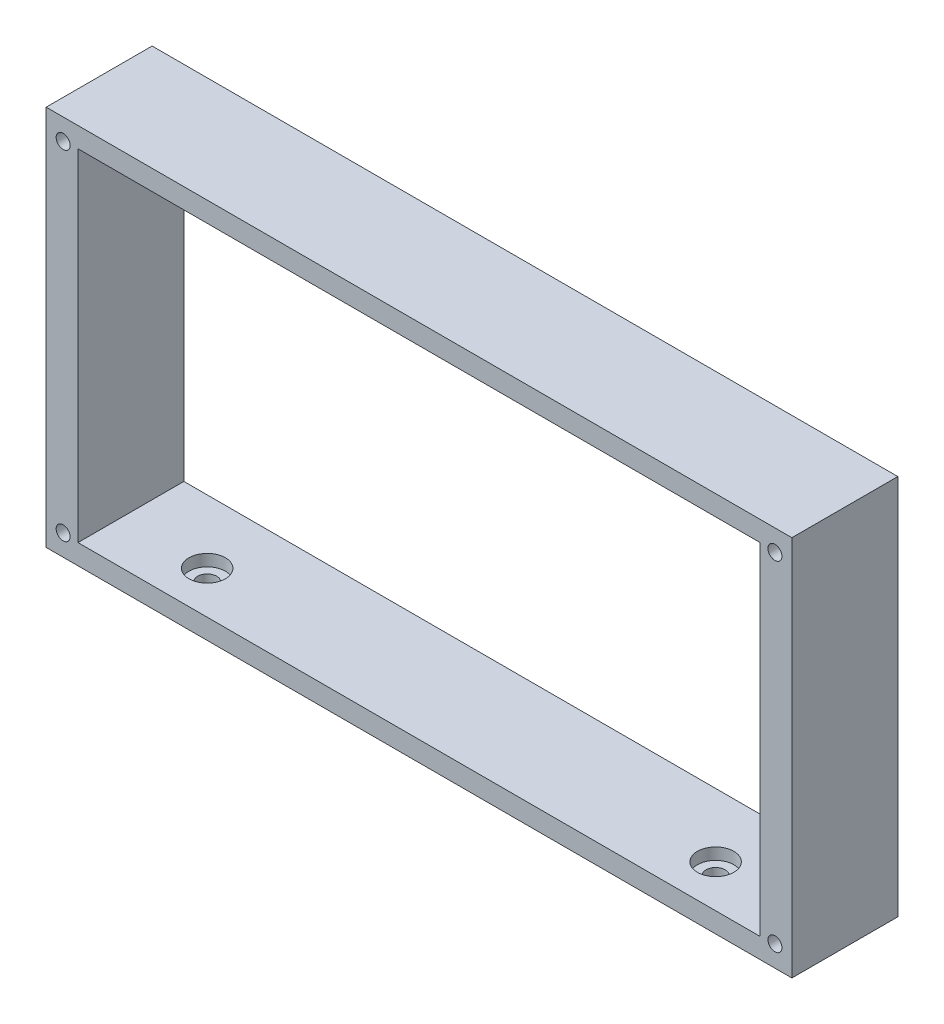
SolidWorks part; units mm, degrees
ref_plane "Front Plane" through (0, 0, 0) normal (0, 0, 1) x (1, 0, 0)
ref_plane "Top Plane" through (0, 0, 0) normal (0, 1, 0) x (1, 0, 0)
ref_plane "Right Plane" through (0, 0, 0) normal (1, 0, 0) x (0, 0, -1)
sketch "Sketch5" plane through (0, 0, 0) normal (0, 0, 1) x (1, 0, 0)
  line L1 (-80.5, -40.25) -> (80.5, -40.25)
  line L2 (-80.5, -40.25) -> (-80.5, 40.25)
  line L3 (-80.5, 40.25) -> (80.5, 40.25)
  line L4 (80.5, -40.25) -> (80.5, 40.25)
  line L5 (-80.5, -40.25) -> (80.5, 40.25) construction
  line L6 (-80.5, 40.25) -> (80.5, -40.25) construction
  line L7 (-88, -45) -> (88, -45)
  line L8 (-88, -45) -> (-88, 45)
  line L9 (-88, 45) -> (88, 45)
  line L10 (88, -45) -> (88, 45)
  line L11 (-88, -45) -> (88, 45) construction
  line L12 (-88, 45) -> (88, -45) construction
  point P0 (0, 0)
  point P6 (0, 0)
  dimension "D1" = 161
  dimension "D2" = 80.5
  dimension "D3" = 176
  dimension "D4" = 90
extrude "Boss-Extrude2" add sketch "Sketch5" along normal blind 25
hole_wizard "M4x0.7 Tapped Hole1" positions "Sketch6" profile "Sketch7" tap size "M4x0.7" standard "ANSI Metric" end condition through all
sketch "Sketch6" plane through (0, 0, 0) normal (0, 0, -1) x (-1, 0, 0)
  line L1 (-84, -40) -> (84, -40)
  line L2 (-84, -40) -> (-84, 40)
  line L3 (-84, 40) -> (84, 40)
  line L4 (84, -40) -> (84, 40)
  line L5 (-84, -40) -> (84, 40) construction
  line L6 (-84, 40) -> (84, -40) construction
  point P1 (0, 0)
  point P2 (84, 40)
  point P115 (-84, -40)
  point P116 (-84, 40)
  point P117 (84, -40)
  dimension "D1" = 168
  dimension "D2" = 80
sketch "Sketch7" plane through (0, 0, 0) normal (1, 0, 0) x (0, 1, 0)
  line L0 (0, 0) -> (0, 25)
  line L1 (0, 25) -> (1.65, 25)
  line L2 (1.65, 25) -> (1.65, 0)
  line L5 (1.65, 0) -> (0, 0)
  line L11 (0, -6.35) -> (0, 107.95) construction
  dimension "Thru Tap Drill Dia." = 3.3
  dimension "Thru Tap Drill Depth" = 25
cosmetic thread "Hole Thread1" parameters "D2"=4
cosmetic thread "Hole Thread2" parameters "D2"=4
cosmetic thread "Hole Thread3" parameters "D2"=4
cosmetic thread "Hole Thread4" parameters "D2"=4
hole_wizard "CBORE for M4 SBHCS1" positions "Sketch8" profile "Sketch10" counterbore size "M4" standard "ANSI Metric" end condition through all
sketch "Sketch8" plane through (0, -40.25, 0) normal (0, 1, 0) x (1, 0, 0)
  line L0 (-60, -15) -> (60, -15)
  line L2 (-88, -25) -> (88, -25) construction
  point P1 (-60, -15)
  point P2 (60, -15)
  point P9 (0, -15)
  dimension "D1" = 120
  dimension "D2" = 10
sketch "Sketch10" plane through (-60, -40.25, 15) normal (1, 0, 0) x (0, 0, 1)
  line L0 (0, 0) -> (0, 4.75)
  line L1 (0, 4.75) -> (2.25, 4.75)
  line L3 (2.25, 4.75) -> (2.25, 2.75)
  line L4 (2.25, 2.75) -> (4.3, 2.75)
  line L5 (4.3, 2.75) -> (4.3, 0)
  line L7 (4.3, 0) -> (0, 0)
  line L11 (0, -6.35) -> (0, 107.95) construction
  dimension "Thru Hole Dia." = 4.5
  dimension "Thru Hole Depth" = 4.75
  dimension "C'Bore Dia." = 8.6
  dimension "C'Bore Depth" = 2.75
hole_wizard "M4x0.7 Tapped Hole2" positions "Sketch11" profile "Sketch12" tap size "M4x0.7" standard "ANSI Metric"
sketch "Sketch11" plane through (0, 0, 0) normal (0, 0, -1) x (-1, 0, 0)
  line L1 (-10, -42.5) -> (10, -42.5)
  line L2 (-10, -42.5) -> (-10, 42.5)
  line L3 (-10, 42.5) -> (10, 42.5)
  line L4 (10, -42.5) -> (10, 42.5)
  line L5 (-10, -42.5) -> (10, 42.5) construction
  line L6 (-10, 42.5) -> (10, -42.5) construction
  line L7 (-88, 45) -> (88, 45) construction
  point P0 (0, 0)
  point P1 (10, 42.5)
  point P48 (-10, -42.5)
  point P49 (-10, 42.5)
  point P50 (10, -42.5)
  dimension "D1" = 20
  dimension "D2" = 2.5
sketch "Sketch12" plane through (0, 0, 0) normal (1, 0, 0) x (0, 1, 0)
  line L0 (0, 0) -> (0, 5.9914)
  line L1 (0, 5.9914) -> (1.65, 5)
  line L2 (1.65, 5) -> (1.65, 0)
  line L5 (1.65, 0) -> (0, 0)
  line L10 (0, 5.9914) -> (-1.65, 5) construction
  line L11 (0, -6.35) -> (0, 107.95) construction
  dimension "Tap Drill Dia." = 3.3
  dimension "Tap Drill Depth" = 5
  dimension "Drill Angle" = 118
cosmetic thread "Hole Thread5" parameters "D1"=25, "D2"=4
cosmetic thread "Hole Thread6" parameters "D1"=25, "D2"=4
cosmetic thread "Hole Thread7" parameters "D1"=25, "D2"=4
cosmetic thread "Hole Thread8" parameters "D1"=25, "D2"=4
